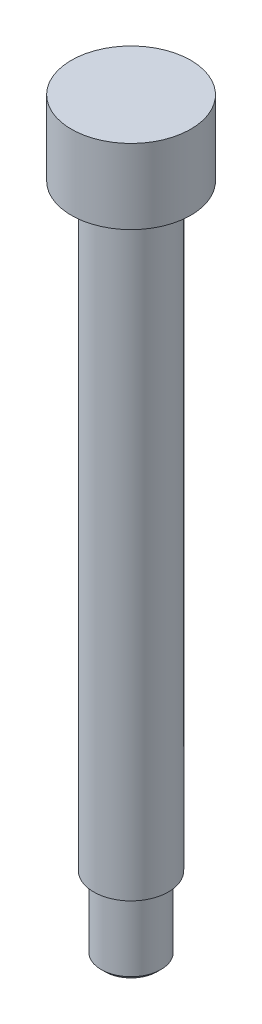
SolidWorks part; units mm, degrees
material "Plain Carbon Steel"
ref_plane "Front Plane" through (0, 0, 0) normal (0, 0, 1) x (1, 0, 0)
ref_plane "Top Plane" through (0, 0, 0) normal (0, 1, 0) x (1, 0, 0)
ref_plane "Right Plane" through (0, 0, 0) normal (1, 0, 0) x (0, 0, -1)
sketch "Sketch1" plane through (0, 0, 0) normal (0, 0, 1) x (1, 0, 0)
  line L0 (0, 0) -> (8, 0)
  line L1 (5, -10) -> (5, -90)
  line L2 (5, -90) -> (4, -90)
  line L3 (4, -90) -> (4, -100)
  line L4 (4, -100) -> (0, -100)
  line L5 (0, -100) -> (0, 0)
  line L6 (0, -105) -> (0, 5) construction
  line L7 (5, -10) -> (8, -10)
  line L8 (8, -10) -> (8, 0)
  dimension "D1" = 5
  dimension "D2" = 5
  dimension "D3" = 8
  dimension "D4" = 10
  dimension "D5" = 16
  dimension "D6" = 10
  dimension "D7" = 100
  dimension "D8" = 10
revolve "Revolve1" add sketch "Sketch1" angle 360 about L6
cosmetic thread "Cosmetic Thread1" parameters "D1"=10, "D2"=6.619
chamfer "Chamfer1" distance 0.5 angle 45 1 edges at (0, -100, -4)
